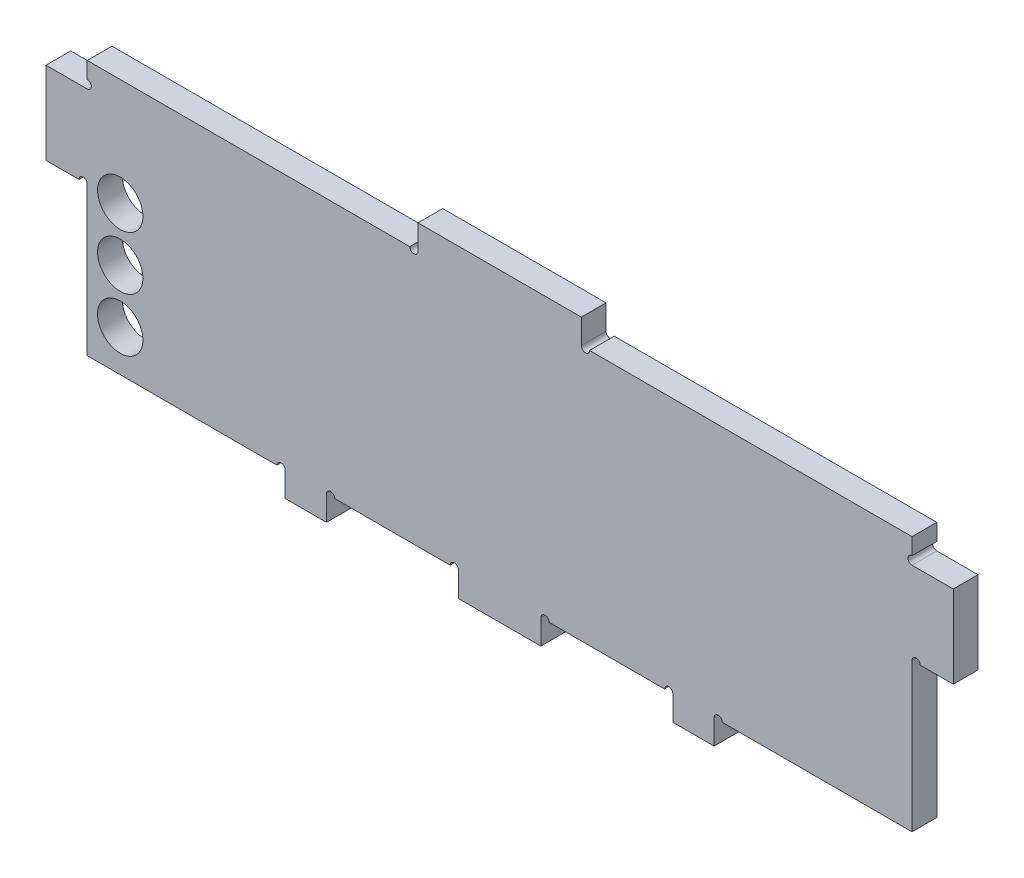
SolidWorks part; units mm, degrees
ref_plane "Front Plane" through (0, 0, 0) normal (0, 0, 1) x (1, 0, 0)
ref_plane "Top Plane" through (0, 0, 0) normal (0, 1, 0) x (1, 0, 0)
ref_plane "Right Plane" through (0, 0, 0) normal (1, 0, 0) x (0, 0, -1)
sketch "Sketch1" plane through (0, 0, 0) normal (0, 0, 1) x (1, 0, 0)
  line L0 (-5, 0) -> (5, 0)
  line L1 (5, 0) -> (5, 3)
  line L2 (5, 3) -> (21, 3)
  line L3 (21, 3) -> (21, 0)
  line L4 (21, 0) -> (26, 0)
  line L5 (26, 0) -> (26, 3)
  line L6 (26, 3) -> (50, 3)
  line L8 (50, 3) -> (50, 21)
  line L9 (50, 21) -> (55, 21)
  line L10 (55, 21) -> (55, 31)
  line L11 (55, 31) -> (50, 31)
  line L12 (50, 34) -> (0, 34)
  line L13 (0, 34) -> (0, 0) construction
  line L14 (-50, 34) -> (0, 34)
  line L15 (-5, 0) -> (-5, 3)
  line L16 (-5, 3) -> (-21, 3)
  line L17 (-21, 3) -> (-21, 0)
  line L18 (-21, 0) -> (-26, 0)
  line L19 (-26, 0) -> (-26, 3)
  line L20 (-26, 3) -> (-50, 3)
  line L21 (-46, 21) -> (-46, 8) construction
  line L22 (-50, 3) -> (-50, 21)
  line L23 (-50, 21) -> (-55, 21)
  line L24 (-55, 21) -> (-55, 31)
  line L25 (-50, 31) -> (-50, 34)
  line L26 (50, 31) -> (50, 34)
  line L27 (-55, 31) -> (-50, 31)
  circle A4 centre (-46, 8) radius 2.75
  circle A5 centre (-46, 14.5) radius 2.75
  circle A6 centre (-46, 21) radius 2.75
  dimension "D13" = 5.5
  dimension "D11" = 4
  dimension "D1" = 5
  dimension "D2" = 5
  dimension "D3" = 3
  dimension "D4" = 16
  dimension "D5" = 55
  dimension "D6" = 5
  dimension "D7" = 5
  dimension "D8" = 10
  dimension "D9" = 31
  dimension "D10" = 3
  dimension "D12" = 5
  dimension "D14" = 13
extrude "Boss-Extrude1" add sketch "Sketch1" along normal blind 3
sketch "Sketch4" plane through (0, 0, 3) normal (0, 0, 1) x (1, 0, 0)
  line L0 (-50, 34) -> (0, 34) construction
  line L1 (-9.9, 34) -> (9.9, 34)
  line L2 (-9.9, 34) -> (-9.9, 37)
  line L3 (-9.9, 37) -> (9.9, 37)
  line L4 (9.9, 34) -> (9.9, 37)
  dimension "D1" = 3
  dimension "D2" = 19.8
extrude "Boss-Extrude2" add sketch "Sketch4" against normal blind 3
sketch "Sketch3" plane through (0, 0, 3) normal (0, 0, 1) x (1, 0, 0)
  line L0 (5, 3) -> (21, 3) construction
  line L1 (26, 3) -> (50, 3) construction
  line L2 (50, 34) -> (0, 34) construction
  line L3 (50, 21) -> (55, 21) construction
  line L4 (-50, 34) -> (0, 34) construction
  line L5 (0, 34) -> (0, 0) construction
  arc A0 (5, 3) -> (6, 3) centre (5.5, 3) cw
  arc A1 (21, 3) -> (20, 3) centre (20.5, 3) ccw
  arc A2 (26, 3) -> (27, 3) centre (26.5, 3) cw
  arc A3 (50, 21) -> (51, 21) centre (50.5, 21) cw
  arc A4 (50, 31) -> (50, 32) centre (50, 31.5) cw
  arc A5 (-50, 31) -> (-50, 32) centre (-50, 31.5) ccw
  arc A6 (-50, 21) -> (-51, 21) centre (-50.5, 21) ccw
  arc A7 (-26, 3) -> (-27, 3) centre (-26.5, 3) ccw
  arc A8 (-21, 3) -> (-20, 3) centre (-20.5, 3) cw
  arc A9 (-5, 3) -> (-6, 3) centre (-5.5, 3) ccw
  arc A10 (9.9, 34) -> (10.9, 34) centre (10.4, 34) ccw
  arc A11 (-9.9, 34) -> (-10.9, 34) centre (-10.4, 34) cw
  line M4 (5, 3) -> (21, 3)
  line M8 (26, 3) -> (50, 3)
  line M11 (50, 21) -> (55, 21)
  line M14 (50, 31) -> (50, 34)
  line M15 (50, 34) -> (9.9, 34)
  line M16 (-50, 34) -> (-50, 31)
  line M19 (-55, 21) -> (-50, 21)
  line M22 (-50, 3) -> (-26, 3)
  line M26 (-21, 3) -> (-5, 3)
  line M60 (-9.9, 34) -> (-50, 34)
  dimension "D1" = 0.5
extrude "Cut-Extrude2" cut sketch "Sketch3" against normal through all contours A4 M14 | A3 M11 | A5 M16 | A6 M19 | A7 M22 | A8 M26 | A9 M26 | A0 M4 | A1 M4 | A2 M8 | A11 M60 | A10 M15 region at (20.5, 3.2122, 3) region at (5.5, 3.2122, 3) region at (26.5, 3.2122, 3) region at (50.5, 21.2122, 3) region at (10.4, 33.7878, 3) region at (49.7878, 31.5, 3) region at (-49.7878, 31.5, 3) region at (-10.4, 33.7878, 3) region at (-50.5, 21.2122, 3) region at (-26.5, 3.2122, 3) region at (-5.5, 3.2122, 3) region at (-20.5, 3.2122, 3)
